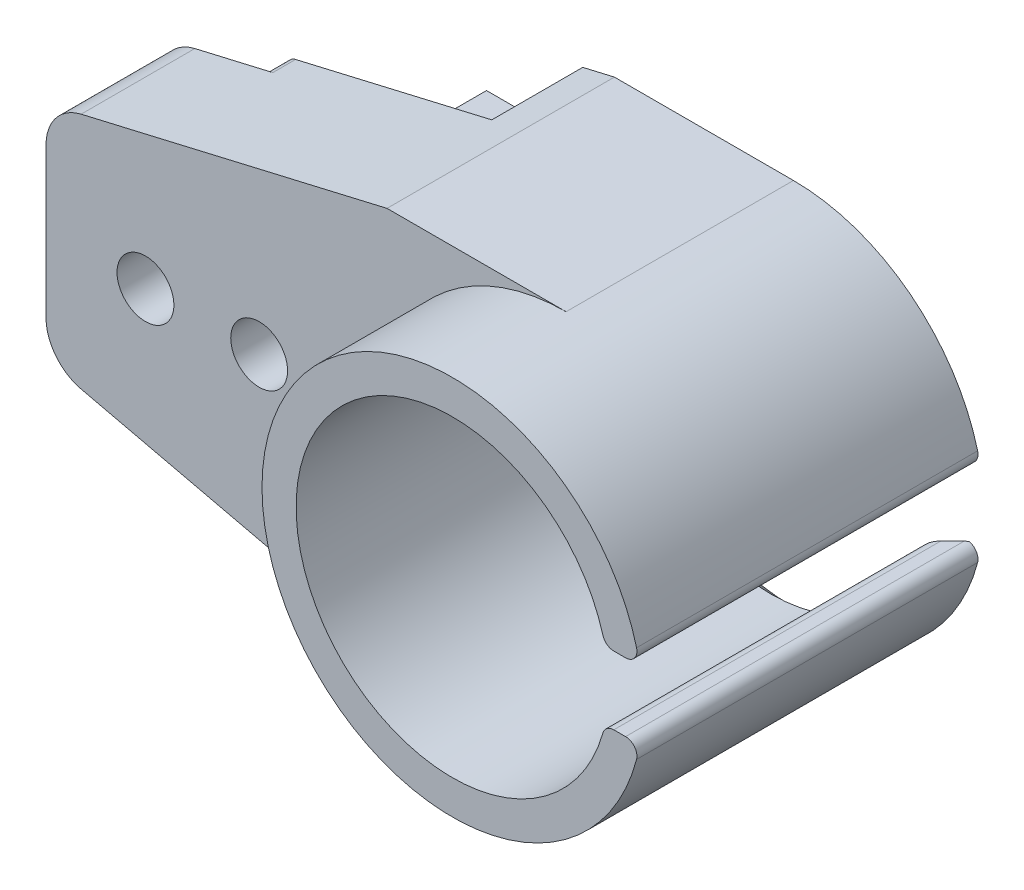
SolidWorks part; units mm, degrees
ref_plane "Plan de face" through (0, 0, 0) normal (0, 0, 1) x (1, 0, 0)
ref_plane "Plan de dessus" through (0, 0, 0) normal (0, 1, 0) x (1, 0, 0)
ref_plane "Plan de droite" through (0, 0, 0) normal (1, 0, 0) x (0, 0, -1)
sketch "Esquisse1" plane through (0, 0, 0) normal (0, 0, 1) x (1, 0, 0)
  line L0 (0, 0) -> (13.75, 0) construction
  line L1 (0, 3) -> (21.7672, 3) construction
  line L2 (0, -3) -> (21.7672, -3) construction
  line L3 (13.4187, 3) -> (16.4792, 3)
  line L4 (16.4792, -3) -> (13.4187, -3)
  line L5 (0, 0) -> (0, 16.75) construction
  line L6 (0, -16.75) -> (-45.75, -16.75)
  line L7 (-45.75, -16.75) -> (-45.75, 16.75)
  line L8 (-45.75, 16.75) -> (0, 16.75)
  circle A0 centre (0, 0) radius 13.75 construction
  arc A1 (13.4187, 3) -> (13.4187, -3) centre (0, 0) ccw
  arc A3 (16.4792, 3) -> (0, 16.75) centre (0, 0) ccw
  arc A4 (16.4792, -3) -> (0, -16.75) centre (0, 0) cw
  circle A5 centre (-37, 0) radius 2.5
  circle A6 centre (-27, 0) radius 2.5
  point P18 (-13.75, 0)
  dimension "D1" = 27.5
  dimension "D2" = 6
  dimension "D3" = 32
  dimension "D4" = 3
  dimension "D6" = 5
  dimension "D5" = 10
  dimension "D7" = 27
extrude "Boss.-Extru.1" add sketch "Esquisse1" along normal blind 30
chamfer "Chanfrein1" distance 2 angle 45 1 edges at (-13.75, 0, 0)
fillet "Congé2" radius 1 4 edges at (16.4792, -3, 15) (16.4792, 3, 15) (13.4187, -3, 16) (13.4187, 3, 16)
sketch "Esquisse2" plane through (0, 0, 0) normal (0, 0, -1) x (-1, 0, 0)
  line L0 (45.75, 10.1) -> (27, 10.1)
  line L1 (45.75, 16.75) -> (45.75, -16.75) construction
  line L2 (27, -10.1) -> (45.75, -10.1)
  line L3 (45.75, -10.1) -> (45.75, 10.1)
  arc A0 (27, 10.1) -> (27, -10.1) centre (27, 0) ccw
  circle A1 centre (27, 0) radius 2.5 construction
  dimension "D1" = 20.2
extrude "Enlèv. mat.-Extru.1" cut sketch "Esquisse2" against normal blind 10
sketch "Esquisse3" plane through (0, 0, 30) normal (0, 0, 1) x (1, 0, 0)
  line L0 (0, 16.75) -> (-45.75, 16.75) construction
  line L1 (0, 16.75) -> (-45.75, 16.75)
  line L2 (-45.75, 16.75) -> (-45.75, -16.75)
  line L3 (-45.75, -16.75) -> (0, -16.75)
  line L4 (-45.75, 16.75) -> (-45.75, -16.75) construction
  arc A1 (0, 16.75) -> (0, -16.75) centre (0, 0) ccw
  arc A2 (16.2008, 4.254) -> (0, 16.75) centre (0, 0) ccw construction
  arc A3 (0, -16.75) -> (16.2008, -4.254) centre (0, 0) ccw construction
extrude "Enlèv. mat.-Extru.2" cut sketch "Esquisse3" against normal blind 10
sketch "Esquisse5" plane through (0, 0, 20) normal (0, 0, 1) x (1, 0, 0)
  line L0 (-15.75, 16.75) -> (-45.75, 9.75)
  line L1 (0, 16.75) -> (-45.75, 16.75) construction
  line L2 (-45.75, 16.75) -> (-45.75, -16.75) construction
  line L3 (-45.75, 9.75) -> (-45.75, 16.75)
  line L4 (-45.75, 16.75) -> (-15.75, 16.75)
  line L5 (-45.75, 0) -> (0, 0) construction
  line L6 (-45.75, -16.75) -> (-15.75, -16.75)
  line L7 (-45.75, -9.75) -> (-45.75, -16.75)
  line L8 (-15.75, -16.75) -> (-45.75, -9.75)
  dimension "D1" = 7
  dimension "D2" = 30
extrude "Enlèv. mat.-Extru.3" cut sketch "Esquisse5" against normal through all
fillet "Congé3" radius 1 2 edges at (-44.25, 10.1, 5) (-44.25, -10.1, 5)
fillet "Congé4" radius 4 2 edges at (-45.75, 9.75, 15) (-45.75, -9.75, 15)
sketch "Esquisse6" plane through (0, 0, 0) normal (0, 0, -1) x (-1, 0, 0)
  line L0 (27, 10.1) -> (47.1758, 10.1)
  line L1 (47.1758, 10.1) -> (47.1758, 16.1)
  line L2 (47.1758, 16.1) -> (9.3302, 16.1)
  line L4 (9.3302, 10.1) -> (27, 10.1)
  line L6 (4.1408, 13.1117) -> (9.3302, 10.1)
  line L7 (4.1408, 13.1117) -> (9.3302, 16.1)
  line L8 (9.3302, 16.1) -> (9.3302, 10.1) construction
  arc A1 (-13.2347, -3.7288) -> (-13.2347, 3.7288) centre (0, 0) ccw construction
  dimension "D1" = 6
  dimension "D2" = 6
extrude "Enlèv. mat.-Extru.4" cut sketch "Esquisse6" against normal blind 8
